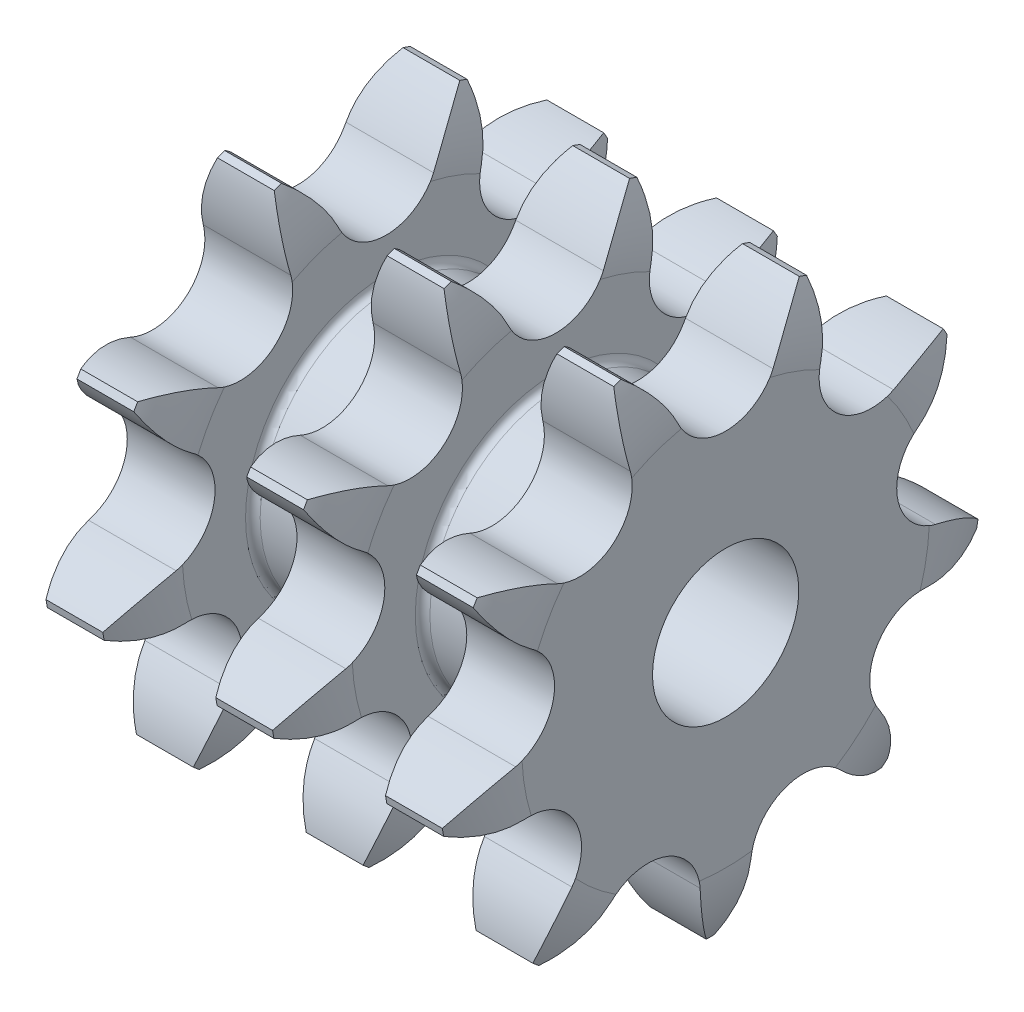
SolidWorks part; units mm, degrees
ref_plane "Plane1" through (0, 0, 0) normal (0, 0, 1) x (1, 0, 0)
ref_plane "Plane2" through (0, 0, 0) normal (0, 1, 0) x (1, 0, 0)
ref_plane "Plane3" through (0, 0, 0) normal (1, 0, 0) x (0, 0, -1)
sketch "Clipboard" plane through (0, 0, 0) normal (0, 1, 0) x (1, 0, 0)
  line L0 (0, 0) -> (12.5436, -1.9867)
  line L1 (-15, 0) -> (100, 0) construction
  line L2 (0, 0) -> (-0.8416, 0.9512)
  line L3 (0, 0) -> (-11.863, 4.5341)
  line L4 (0, 0) -> (3.0618, 0.4849)
  line L5 (0, 0) -> (-2.8109, -1.0484)
  line L6 (0, 0) -> (-29.0469, -19.598)
  line L7 (-0.8416, 0.9512) -> (35.5852, 8.6939)
  line L8 (-76.2, 38.1) -> (-75.2, 38.1)
  line L9 (-73.4259, 41.6592) -> (-72.8306, 41.7344)
  line L10 (-73.4741, 12.7512) -> (-59.5541, 12.7512)
  circle A0 centre (0, 0) radius 4.255
  circle A1 centre (0, 0) radius 10.8715
  circle A2 centre (0, 0) radius 25
  dimension "Num_teeth" = 9
  dimension "Thickness" = 35.04
  dimension "Fillet_rad" = 0.6
sketch "BasProSke" plane through (0, 0, 0) normal (0, 1, 0) x (1, 0, 0)
  line L0 (-10, 0) -> (60, 0) construction
  line L1 (0, 0) -> (0, 16.7129)
  line L2 (0, 0) -> (35.04, 0)
  line L3 (35.04, 0) -> (35.04, 16.7129)
  line L4 (33.77, 22.2487) -> (1.27, 22.2487)
  arc A0 (0, 16.7129) -> (1.27, 22.2487) centre (12.7, 16.7129) cw
  arc A1 (35.04, 16.7129) -> (33.77, 22.2487) centre (22.34, 16.7129) ccw
  dimension "D1" = 12.7
  dimension "Thickness" = 35.04
  dimension "Diameter" = 44.4973
  dimension "G1" = 1.27
revolve "Base-Revolve" add sketch "BasProSke" angle 360 about L0
sketch "GrvSke" plane through (0, 0, 0) normal (0, 1, 0) x (1, 0, 0)
  line L0 (7.2, 16.7129) -> (7.2, 11.5305)
  line L1 (7.8, 10.9305) -> (13.32, 10.9305)
  line L2 (13.92, 11.5305) -> (13.92, 16.7129)
  line L3 (5.93, 22.2487) -> (15.19, 22.2487)
  line L4 (10.56, 0) -> (10.56, 52.07) construction
  line L5 (-10, 0) -> (60, 0) construction
  line L6 (0, 0) -> (35.56, 0) construction
  arc A0 (13.92, 16.7129) -> (15.19, 22.2487) centre (26.62, 16.7129) cw
  arc A1 (7.2, 16.7129) -> (5.93, 22.2487) centre (-5.5, 16.7129) ccw
  arc A2 (7.2, 11.5305) -> (7.8, 10.9305) centre (7.8, 11.5305) ccw
  arc A3 (13.32, 10.9305) -> (13.92, 11.5305) centre (13.32, 11.5305) ccw
  dimension "D1" = 12.7
  dimension "Diameter" = 44.4973
  dimension "Fillet_rad" = 0.6
  dimension "G1" = 1.27
  dimension "Grv_width" = 6.72
revolve "Groove" cut sketch "GrvSke" angle 360 about L6
pattern_linear "Grooves" count 2 spacing 13.92 along (1, 0, 0) of "Groove"
sketch "TooCutSke" plane through (0, 0, 0) normal (1, 0, 0) x (0, 0, -1)
  line L0 (0, 18.6087) -> (3.8949, 16.7925) construction
  line L1 (0, 0) -> (0, 107) construction
  line L2 (0, 18.6087) -> (-10, 18.6087) construction
  line L3 (0, 18.6087) -> (-3.8949, 16.7925) construction
  arc A0 (3.8949, 16.7925) -> (7.8075, 21.3669) centre (14.0756, 12.0451) cw
  arc A1 (3.8949, 16.7925) -> (-3.8949, 16.7925) centre (0, 18.6087) cw
  arc A2 (-3.8949, 16.7925) -> (-7.8075, 21.3669) centre (-14.0756, 12.0451) ccw
  arc A3 (7.8075, 21.3669) -> (-7.8075, 21.3669) centre (0, 0) ccw
extrude "ToothCut" cut sketch "TooCutSke" along normal through all
pattern_circular "TeethCuts" count 9 every 40 about axis through (-10, 0, 0) along (1, 0, 0) of "ToothCut"
sketch "HubNeaOneSke" plane through (0, 0, 0) normal (-1, 0, 0) x (0, 0, 1)
  circle A0 centre (0, 0) radius 10.8715
  dimension "Diameter" = 21.743
extrude "HubNearOne" [suppressed] add sketch "HubNeaOneSke" along normal blind 2.2005
fillet "HubNearOneFillet" [suppressed] radius 0.6
sketch "HubNeaBotSke" plane through (0, 0, 0) normal (-1, 0, 0) x (0, 0, 1)
  circle A0 centre (0, 0) radius 10.8715
  dimension "Diameter" = 21.743
extrude "HubNearBoth" [suppressed] add sketch "HubNeaBotSke" along normal blind 1.1003
fillet "HubNearBothFillet" [suppressed] radius 0.6
ref_plane "FarPln" through (35.04, 0, 0) normal (1, 0, 0) x (0, 0, -1)
sketch "HubFarSke" plane through (35.04, 0, 0) normal (1, 0, 0) x (0, 0, -1)
  circle A0 centre (0, 0) radius 10.8715
  dimension "Diameter" = 21.743
extrude "HubFar" [suppressed] add sketch "HubFarSke" along normal blind 1.1003
fillet "HubFarFillet" [suppressed] radius 0.6
sketch "BorSke" plane through (0, 0, 0) normal (1, 0, 0) x (0, 0, -1)
  circle A0 centre (0, 0) radius 6
  dimension "Diameter" = 12
extrude "Bore" cut sketch "BorSke" along normal mid plane 74.481
sketch "KeySke" plane through (0, 0, 0) normal (1, 0, 0) x (0, 0, -1)
  line L0 (-1, 0) -> (-1, 7)
  line L1 (-1, 7) -> (1, 7)
  line L2 (1, 7) -> (1, 0)
  line L3 (0, 0) -> (0, 34) construction
  line L4 (-1, 0) -> (1, 0)
  dimension "Offset" = 7
  dimension "Width" = 2
extrude "Keyway" [suppressed] cut sketch "KeySke" along normal mid plane 74.481
pattern_circular "Keyway2" [suppressed] count 2 every 90 about axis through (-10, 0, 0) along (1, 0, 0)
equation "' \"Pitch@Clipboard\" = 12.7"
equation "' \"Num_strands@Clipboard\" = 3"
equation "' \"Num_teeth@Clipboard\" = 9"
equation "' \"Hub_dia@Clipboard\" = 50"
equation "' \"Overall_len@Clipboard\" = 3"
equation "' \"Diameter@BorSke\" = 12"
equation "' \"T_dim@Clipboard\" = 1"
equation "' \"Width@KeySke\" = 2"
equation "' \"Dr@Clipboard\" = 8.51"
equation "' \"Face_width@Clipboard\" = 7.2"
equation "' \"Side_radius@Clipboard\" = 12.7"
equation "' \"Side_relief@Clipboard\" = 1.27"
equation "' \"Transv_pitch@Clipboard\" = 13.92"
equation "' \"Show_teeth@Clipboard\" = 9"
equation "' \"Fillet_rad@Clipboard\" = 0.6"
equation "' \"Plate_wid@Clipboard\" = 11.8"
equation "\"Num_teeth@Clipboard\" = int( \"Num_teeth@Clipboard\" )"
equation "\"Num_teeth@Clipboard\" = ((sgn( \"Num_teeth@Clipboard\" - 5.0)+1)*( \"Num_teeth@Clipboard\" - 5.0))/2 +5.0"
equation "\"Num_teeth@Clipboard\" = ((sgn( \"Num_teeth@Clipboard\" - 200.0)-1)*( \"Num_teeth@Clipboard\" - 200.0))/-2 +200.0"
equation "\"MHD@Clipboard\" = \"Pitch@Clipboard\" * (1.0 / tan(3.14159265 / \"Num_teeth@Clipboard\" )) - 1.05 * \"Plate_wid@Clipboard\" - 0.76"
equation "\"Thickness@Clipboard\"  = \"Face_width@Clipboard\" + (\"Num_strands@Clipboard\" - 1) * \"Transv_pitch@Clipboard\""
equation "\"OAL@Clipboard\" = \"Thickness@Clipboard\" + 2 * \"Fillet_rad@Clipboard\" + 1"
equation "\"MHD@Clipboard\" = ((sgn( \"MHD@Clipboard\" - \"Hub_dia@Clipboard\" )-1)*( \"MHD@Clipboard\" - \"Hub_dia@Clipboard\" ))/-2+ \"Hub_dia@Clipboard\""
equation "\"OAL@Clipboard\" = ((sgn( \"OAL@Clipboard\" - \"Overall_len@Clipboard\" )+1)*( \"OAL@Clipboard\" - \"Overall_len@Clipboard\" ))/2 + \"Overall_len@Clipboard\" + 0.0005"
equation "\"Num_teeth@TeethCuts\" = int( \"Show_teeth@Clipboard\" ) + 1"
equation "\"Num_teeth@TeethCuts\" = ((sgn( \"Num_teeth@TeethCuts\" - \"Num_teeth@Clipboard\" )-1)*( \"Num_teeth@TeethCuts\" - \"Num_teeth@Clipboard\" ))/-2+ \"Num_teeth@Clipboard\""
equation "\"Num_teeth@TeethCuts\" = ((sgn( \"Num_teeth@TeethCuts\" - 2.0)+1)*( \"Num_teeth@TeethCuts\" - 2.0))/2 +2.0"
equation "\"Angle@TeethCuts\" = 360.0 / \"Num_teeth@Clipboard\""
equation "\"Seat_radius@TooCutSke\" = ( \"Pitch@Clipboard\" / 2.0) / sin(3.14159265 / \"Num_teeth@Clipboard\" ) - \"Dr@Clipboard\" / 2.0 + \"Dr@Clipboard\" * 0.505"
equation "\"R1@TooCutSke\"  = \"Dr@Clipboard\" * 0.505"
equation "\"X@TooCutSke\" = 140.0 - (90.0 / \"Num_teeth@Clipboard\")"
equation "\"R2@TooCutSke\" = 0.12 * \"Dr@Clipboard\" * ( \"Num_teeth@Clipboard\" + 2.0)"
equation "\"Overcut@TooCutSke\" = 0.5 + 0.625 * \"Pitch@Clipboard\" - 0.5 * \"Dr@Clipboard\"  +  \"Pitch@Clipboard\" / 2.0 / sin(3.14159265 / \"Num_teeth@Clipboard\" )"
equation "\"Diameter@BasProSke\" = 2.0 * ( 0.625 * \"Pitch@Clipboard\" - 0.5 * \"Dr@Clipboard\"  +  \"Pitch@Clipboard\" / 2.0 / sin(3.14159265 / \"Num_teeth@Clipboard\" ))"
equation "\"Thickness@BasProSke\"  = \"Thickness@Clipboard\""
equation "\"G1@BasProSke\" =  \"Side_relief@Clipboard\""
equation "\"G2@BasProSke\" =  \"Side_relief@Clipboard\""
equation "\"D1@BasProSke\" =  \"Side_radius@Clipboard\""
equation "\"Diameter@GrvSke\" = \"Diameter@BasProSke\""
equation "\"G1@GrvSke\" = \"Side_relief@Clipboard\""
equation "\"D1@GrvSke\" = \"Side_radius@Clipboard\""
equation "\"Grv_diam@GrvSke\" =  \"Pitch@Clipboard\" * (1.0 / tan(3.14159265 / \"Num_teeth@Clipboard\" ))- 1.04 * \"Plate_wid@Clipboard\" - 0.76"
equation "\"Grv_width@GrvSke\" =  \"Transv_pitch@Clipboard\" - \"Face_width@Clipboard\""
equation "\"Offset@GrvSke\" = \"Grv_width@GrvSke\" / 2.0 + \"Face_width@Clipboard\""
equation "\"Fillet_rad@GrvSke\" = \"Fillet_rad@Clipboard\""
equation "\"Offset@Grooves\" = \"Transv_pitch@Clipboard\""
equation "\"Num_grvs@Grooves\" = \"Num_strands@Clipboard\""
equation "\"Num_grvs@Grooves\" = \"Num_grvs@Grooves\" - 1 * sgn( \"Num_grvs@Grooves\" -1)"
equation "\"Diameter@HubNeaOneSke\" = \"MHD@Clipboard\""
equation "\"Length@HubNearOne\" = \"OAL@Clipboard\" - \"Thickness@BasProSke\""
equation "\"Diameter@HubNeaBotSke\" = \"MHD@Clipboard\""
equation "\"Length@HubNearBoth\" = ( \"OAL@Clipboard\" - \"Thickness@BasProSke\" ) / 2.0"
equation "\"D1@HubNearOneFillet\" = \"Fillet_rad@Clipboard\""
equation "\"D1@HubNearBothFillet\" = \"Fillet_rad@Clipboard\""
equation "\"Thickness@FarPln\" = \"Thickness@BasProSke\""
equation "\"Diameter@HubFarSke\" = \"MHD@Clipboard\""
equation "\"Length@HubFar\" = ( \"OAL@Clipboard\" - \"Thickness@BasProSke\" ) / 2.0"
equation "\"D1@HubFarFillet\" = \"Fillet_rad@Clipboard\""
equation "\"D1@Bore\" = \"OAL@Clipboard\" * 2.0"
equation "\"D1@Keyway\" = \"OAL@Clipboard\" * 2.0"
equation "\"Offset@KeySke\" = \"T_dim@Clipboard\" + \"Diameter@BorSke\" / 2.0"
